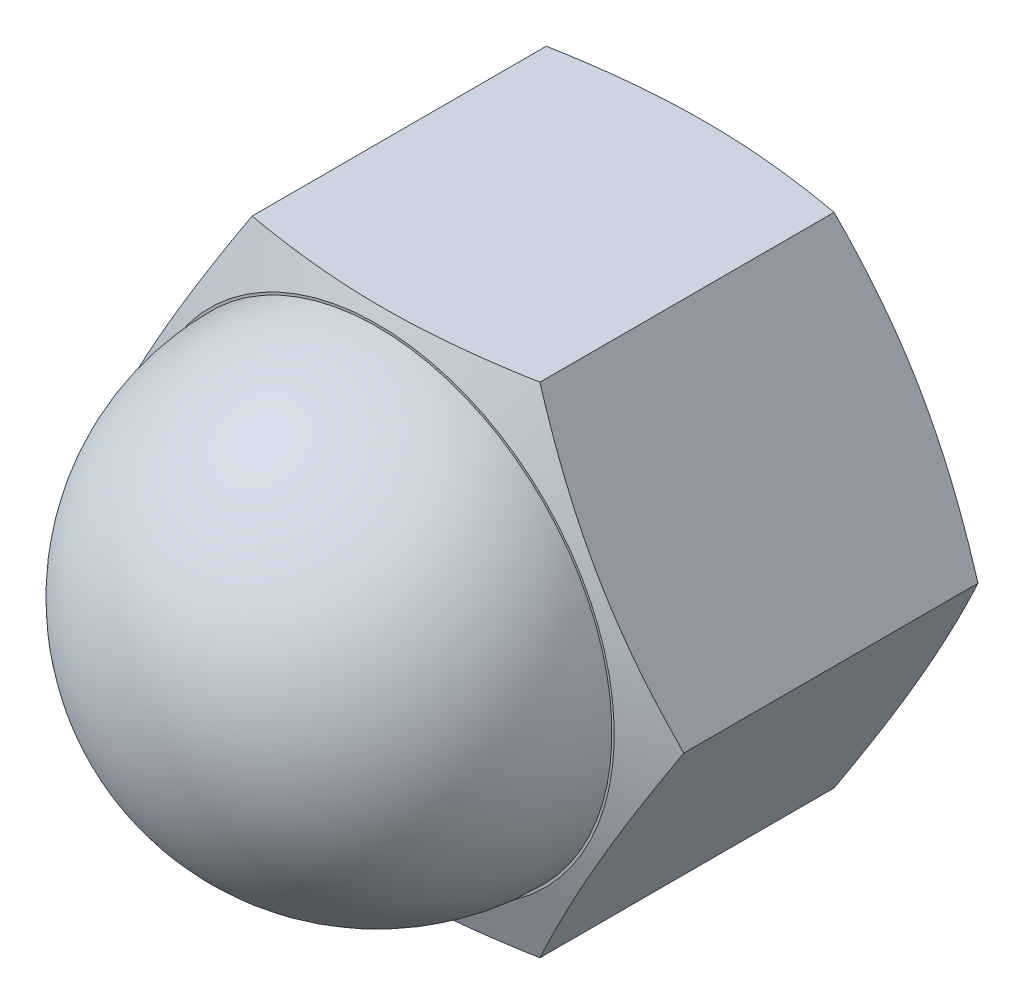
SolidWorks part; units mm, degrees
ref_plane "Front" through (0, 0, 0) normal (0, 0, 1) x (1, 0, 0)
ref_plane "Top" through (0, 0, 0) normal (0, 1, 0) x (1, 0, 0)
ref_plane "Right" through (0, 0, 0) normal (1, 0, 0) x (0, 0, -1)
sketch "Sketch1" plane through (0, 0, 0) normal (0, 0, 1) x (1, 0, 0)
  line L1 (5.6465, 0) -> (2.8232, 4.89)
  line L2 (2.8232, 4.89) -> (-2.8232, 4.89)
  line L3 (-2.8232, 4.89) -> (-5.6465, 0)
  line L4 (-5.6465, 0) -> (-2.8232, -4.89)
  line L5 (-2.8232, -4.89) -> (2.8232, -4.89)
  line L6 (2.8232, -4.89) -> (5.6465, 0)
  circle A0 centre (0, 0) radius 4.89 construction
  circle A1 centre (0, 0) radius 2.5
extrude "BaseNut" add sketch "Sketch1" against normal blind 6.5
cosmetic thread "ThreadCosmetic1" [suppressed] parameters "D1"=5, "D2"=6
sketch "Sketch2" plane through (0, 0, 0) normal (0, 1, 0) x (1, 0, 0)
  line L0 (-4.6455, 6.5) -> (-5.6465, 6.5)
  line L2 (-5.6465, 6.5) -> (-5.6465, 6.1357)
  line L4 (-5.6465, 6.1357) -> (-4.6455, 6.5)
  line L5 (0, 11.5694) -> (0, -9.1399) construction
  line L7 (-7.1748, 3.25) -> (8.0192, 3.25) construction
  line L8 (-5.6465, 0.3643) -> (-4.6455, 0)
  line L9 (-5.6465, 0) -> (-5.6465, 0.3643)
  line L10 (-4.6455, 0) -> (-5.6465, 0)
  line L11 (-2.8232, 0) -> (-5.6465, 0) construction
  dimension "D1" = 9.291
  dimension "h1" = 3.25
revolve "DoubleChamfer" cut sketch "Sketch2" angle 360 about L5
sketch "Sketch3" plane through (-4.6, 0, -7.9176) normal (0, 1, 0) x (-1, 0, 0)
  line L2 (-4.6, 6.4176) -> (-8.9486, 6.4176)
  line L3 (-4.6, 5.0684) -> (-4.6, 6.4176) construction
  line L4 (-7.1, 1.4176) -> (-2.1, 1.4176) construction
  line L8 (-4.6, 12.5176) -> (-4.6, 6.4176)
  line L11 (-9.2455, 1.4176) -> (0.0455, 1.4176) construction
  arc A0 (-4.6, 12.5176) -> (-8.9486, 6.4176) centre (-4.6, 7.9176) ccw
  dimension "h" = 6.5
  dimension "b" = 5
revolve "Crown" add sketch "Sketch3" angle 360 about L3
chamfer "EndChamfer" distance 0.65 angle 30 1 edges at (2.5, 0, -6.5) first distance on face at (2.5, 0, -6.5)
sketch "Sketch4" plane through (0, 0, 0) normal (0, 1, 0) x (1, 0, 0)
  line L0 (0, 7.6611) -> (0, -9.4764) construction
  line L1 (2, 6.1) -> (2, 5.6)
  line L2 (2, 5.6) -> (2.5, 5.6)
  line L3 (2.5, 5.6) -> (2.933, 5.85)
  line L4 (2.933, 5.85) -> (2.5, 6.1)
  line L5 (2, 6.1) -> (2.5, 6.1)
  line L6 (-2.5, 5.85) -> (2.5, 5.85) construction
  dimension "D1" = 5
  dimension "D2" = 0.5
revolve "Cut-Revolve10" [suppressed] cut sketch "Sketch4" angle 360 about L0
pattern_linear "LPattern10" [suppressed] count 11 spacing 0.6 along (0, 0, 1) of bodies 104
equation "\"D1@Sketch2\" = 0.95 * \"s@Sketch1\""
equation "\"h1@Sketch2\" = \"h@Sketch3\" / 2"
equation "\"h@BaseNut\" = \"h@Sketch3\""
equation "\"D1@Sketch4\" = \"d@Sketch1\""
equation "\"D2@Sketch4\" =  ( \"D2@ThreadCosmetic1\" - \"d@Sketch1\" )  / 2"
equation "\"D3@LPattern10\" = \"D2@Sketch4\" * 1.2"
equation "\"D1@LPattern10\" = \"h@BaseNut\" / \"D3@LPattern10\""
